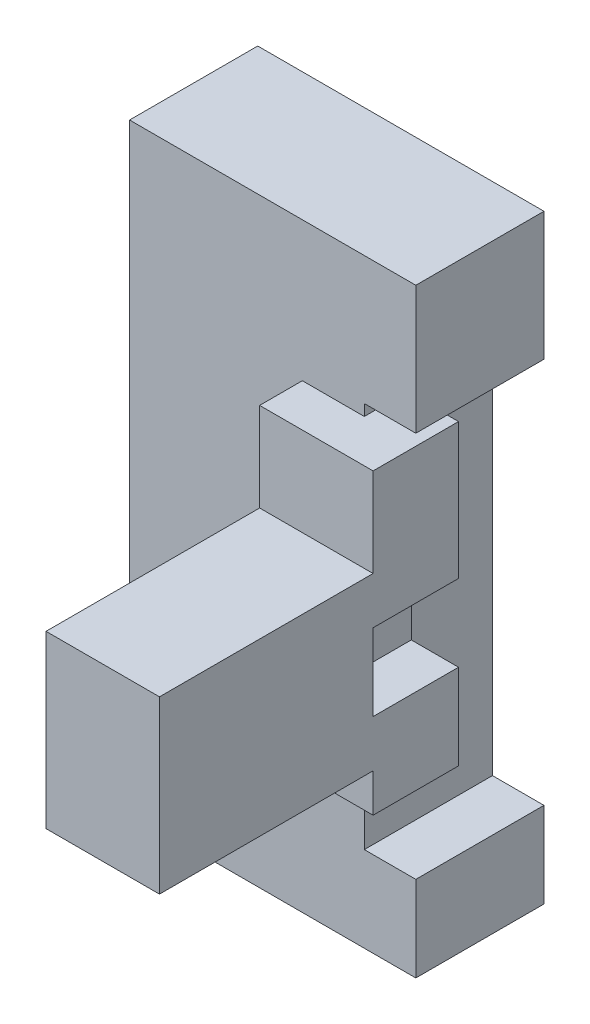
SolidWorks part; units mm, degrees
ref_plane "Alzado" through (0, 0, 0) normal (0, 0, 1) x (1, 0, 0)
ref_plane "Planta" through (0, 0, 0) normal (0, 1, 0) x (1, 0, 0)
ref_plane "Vista lateral" through (0, 0, 0) normal (1, 0, 0) x (0, 0, -1)
sketch "Croquis1" plane through (0, 0, 0) normal (0, 0, 1) x (1, 0, 0)
  line L0 (44.7148, -7.1211) -> (44.7148, -7.6211) construction
  line L1 (45.1148, -5.8211) -> (45.2206, -5.8211) construction
  line L2 (44.7148, -7.6211) -> (44.1148, -7.6211)
  line L6 (45.2206, -7.6211) -> (44.7148, -7.6211)
  line L7 (44.1148, -7.6211) -> (43.1148, -7.6211) construction
  line L8 (44.1148, -4.6411) -> (44.1148, -2.6411) construction
  line L9 (44.1148, -7.6211) -> (44.1148, -9.6211) construction
  line L10 (45.2206, -7.6211) -> (45.2206, -9.6211)
  line L11 (45.2206, -9.6211) -> (44.1148, -9.6211)
  line L12 (44.1148, -9.6211) -> (43.1148, -9.6211)
  line L13 (43.1148, -9.6211) -> (43.1148, -2.6411)
  line L14 (43.1148, -2.6411) -> (45.2206, -2.6411)
  line L15 (45.2206, -2.6411) -> (45.2206, -4.6411)
  line L16 (45.2206, -4.6411) -> (45.2206, -5.8211)
  line L17 (45.2206, -5.8211) -> (44.1148, -5.8211)
  line L18 (44.1148, -5.8211) -> (44.1148, -7.6211)
  dimension "D1" = 43.1148
  dimension "D2" = 44.1148
  dimension "D3" = 45.2206
  dimension "D4" = 2.6411
  dimension "D5" = 4.6411
  dimension "D6" = 5.8211
  dimension "D7" = 7.6211
extrude "Saliente-Extruir1" add sketch "Croquis1" along normal blind 2
sketch "Croquis2" plane through (0, 0, 2) normal (0, 0, 1) x (1, 0, 0)
  line L0 (44.1148, -6.7211) -> (44.1148, -4.7211) construction
  line L1 (44.1148, -7.6211) -> (44.1148, -5.8211) construction
  line L2 (44.1148, -6.7211) -> (44.1148, -8.7211) construction
  line L3 (45.2206, -5.8211) -> (45.2206, -2.6411) construction
  line L4 (45.2206, -4.7211) -> (42.7206, -4.7211)
  line L5 (45.2206, -4.7211) -> (45.2206, -8.7211)
  line L6 (45.2206, -8.7211) -> (42.7206, -8.7211)
  line L7 (42.7206, -4.7211) -> (42.7206, -8.7211)
  line L8 (45.2206, -7.6211) -> (44.1148, -7.6211) construction
  dimension "D1" = 1.3941
  dimension "D2" = 2.9
extrude "Saliente-Extruir2" add sketch "Croquis2" along normal blind 5
sketch "Croquis3" plane through (0, 0, 0) normal (0, 0, -1) x (-1, 0, 0)
  line L0 (-44.0148, -2.3777) -> (-44.0148, -9.421)
  line L5 (-44.0148, -2.3777) -> (-45.2206, -2.3777)
  line L6 (-45.2206, -2.3777) -> (-45.2206, 0.6223)
  line L7 (-45.2206, 0.6223) -> (-40.2206, 0.6223)
  line L8 (-40.2206, 0.6223) -> (-40.2206, -12.421)
  line L11 (-40.2206, -12.421) -> (-40.2206, -13.421)
  line L12 (-40.2206, -13.421) -> (-45.2206, -13.421)
  line L13 (-45.2206, -13.421) -> (-45.2206, -11.421)
  line L17 (-45.2206, -11.421) -> (-44.0148, -11.421)
  line L18 (-44.0148, -11.421) -> (-44.0148, -9.421)
  line L19 (-45.2206, -9.6211) -> (-45.2206, -7.6211) construction
  line L20 (-43.1148, -9.6211) -> (-45.2206, -9.6211) construction
  dimension "D1" = 1.2059
  dimension "D2" = 5
  dimension "D3" = 0.2001
  dimension "D4" = 7.2434
  dimension "D5" = 10.2434
  dimension "D6" = 1.7999
  dimension "D7" = 2.7999
extrude "Saliente-Extruir3" add sketch "Croquis3" along normal blind 2 and the other way blind 1
sketch "Croquis4" plane through (43.1148, 0, 0) normal (-1, 0, 0) x (0, 0, 1)
  line L0 (1, -2.6411) -> (2, -2.6411)
  line L1 (1, -13.421) -> (1, 0.6223) construction
  line L2 (2, -2.6411) -> (1, -2.6411) construction
  line L3 (2, -2.6411) -> (2, -4.7211)
  line L4 (2, -4.7211) -> (7, -4.7211)
  line L5 (7, -4.7211) -> (2, -4.7211) construction
  line L6 (7, -4.7211) -> (7, -8.7211)
  line L7 (7, -8.7211) -> (2, -8.7211)
  line L8 (2, -8.7211) -> (2, -9.6211) construction
  line L9 (7, -8.7211) -> (2, -8.7211) construction
  line L10 (2, -8.7211) -> (2, -9.6211)
  line L11 (2, -9.6211) -> (1, -9.6211)
  line L12 (2, -9.6211) -> (1, -9.6211) construction
  line L13 (1, -9.6211) -> (1, -2.6411)
  line L14 (1, -2.6411) -> (1, -9.6211) construction
  dimension "D1" = 6
extrude "Saliente-Extruir4" add sketch "Croquis4" along normal blind 0.55
sketch "Croquis5" plane through (40.2206, 0, 0) normal (-1, 0, 0) x (0, 0, 1)
  line L0 (1, 0.6223) -> (-2, 0.6223) construction
  line L1 (-2, 0.6223) -> (1, 0.6223)
  line L2 (-2, 0.6223) -> (-2, -13.421)
  line L3 (-2, -13.421) -> (1, -13.421)
  line L4 (1, 0.6223) -> (1, -13.421)
  line L5 (-2, -13.421) -> (-2, 0.6223) construction
  line L6 (1, -13.421) -> (-2, -13.421) construction
  dimension "D1" = 3
extrude "Saliente-Extruir5" add sketch "Croquis5" along normal blind 1.7
